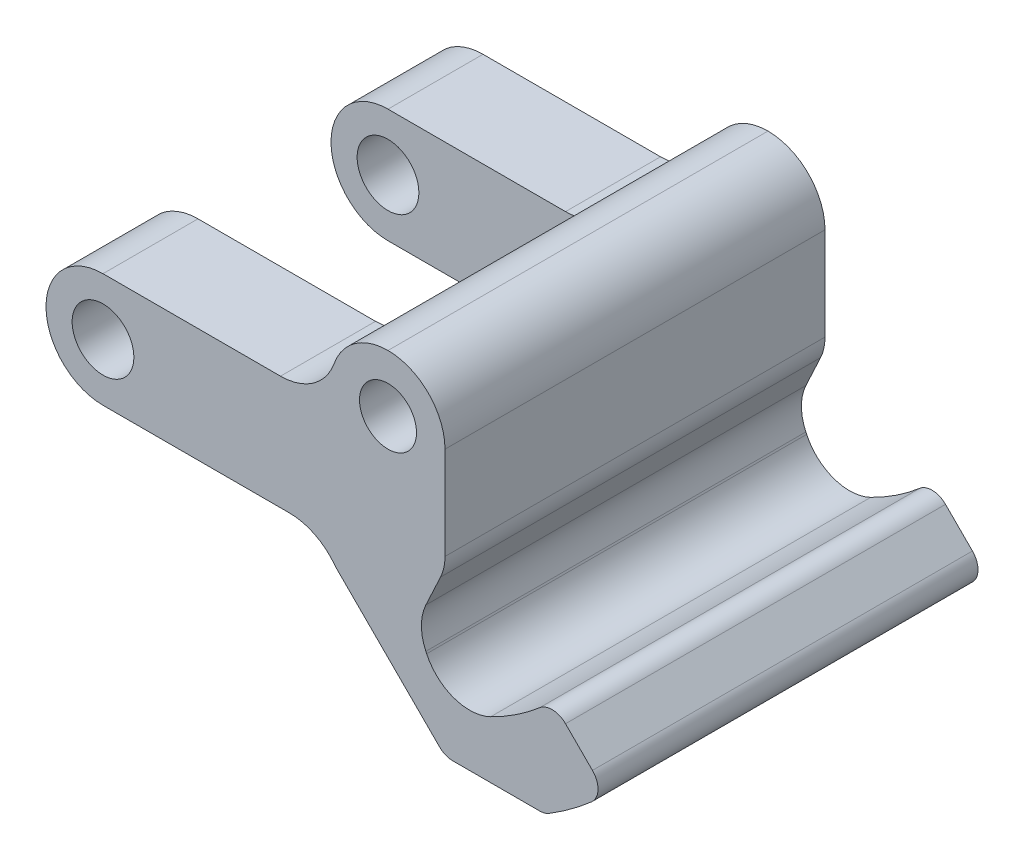
SolidWorks part; units mm, degrees
material "PBT General Purpose"
ref_plane "Front Plane" through (0, 0, 0) normal (0, 0, 1) x (1, 0, 0)
ref_plane "Top Plane" through (0, 0, 0) normal (0, 1, 0) x (1, 0, 0)
ref_plane "Right Plane" through (0, 0, 0) normal (1, 0, 0) x (0, 0, -1)
sketch "Sketch2" plane through (0, 0, 0) normal (0, 0, 1) x (1, 0, 0)
  line L1 (-6, 6) -> (6, 6)
  line L2 (-6, 6) -> (-6, -16)
  line L4 (6, 6) -> (6, -10.8869)
  line L5 (17.3241, -17.3241) -> (22.981, -22.981)
  line L6 (0, 0) -> (17.3241, -17.3241) construction
  line L7 (0, -24.5) -> (0, 0) construction
  line L10 (-6, -16) -> (6, -28)
  line L11 (6, -10.8869) -> (3, -17.3204)
  line L12 (3, -17.3204) -> (6, -23.7539)
  line L13 (6, -28) -> (16.5, -28)
  arc A0 (6, -23.7539) -> (17.3241, -17.3241) centre (0, 0) ccw
  arc A1 (16.5, -28) -> (22.981, -22.981) centre (0, 0) ccw
  circle A2 centre (0, 0) radius 3
  arc A3 (0, -24.5) -> (6, -23.7539) centre (0, 0) ccw construction
  dimension "D2" = 6
  dimension "D5" = 24.5
  dimension "D3" = 12
  dimension "D4" = 45
  dimension "D6" = 8
  dimension "D8" = 45
  dimension "D9" = 25
  dimension "D10" = 25
  dimension "D11" = 3
  dimension "D7" = 28
extrude "Boss-Extrude1" add sketch "Sketch2" along normal mid plane 40
fillet "Fillet1" radius 6 2 edges at (6, 6, 0) (-6, 6, 0)
fillet "Fillet2" radius 2 5 edges at (22.981, -22.981, 0) (17.3241, -17.3241, 0) (-6, -16, 0) (16.5, -28, 0) (6, -28, 0)
fillet "Fillet4" radius 5 3 edges at (6, -10.8869, 0) (3, -17.3204, 0) (6, -23.7539, 0)
sketch "Sketch3" plane through (0, 0, 20) normal (0, 0, 1) x (1, 0, 0)
  line L0 (-6, -2) -> (-36, -2)
  line L1 (-6, 0) -> (-6, -15.1716) construction
  line L2 (-36, -2) -> (-36, -14)
  line L3 (-36, -14) -> (-6, -14)
  line L4 (-6, -14) -> (-6, -2)
  line L5 (-30, -8) -> (-36, -8) construction
  circle A0 centre (-30, -8) radius 3.25
  dimension "D2" = 6
  dimension "D1" = 6.5
  dimension "D3" = 8
  dimension "D4" = 12
  dimension "D5" = 30
extrude "Boss-Extrude2" add sketch "Sketch3" against normal blind 10
fillet "Fillet3" radius 6 4 edges at (-36, -14, 15) (-36, -2, 15) (-6, -14, 15) (-6, -2, 15)
mirror "Mirror1" about plane through (0, 0, 0) normal (0, 0, 1) of "Fillet3", "Boss-Extrude2"
equation "\"D4@Sketch2\"=70-25"
equation "\"D2@Sketch3\"=\"D4@Sketch3\"/2"
